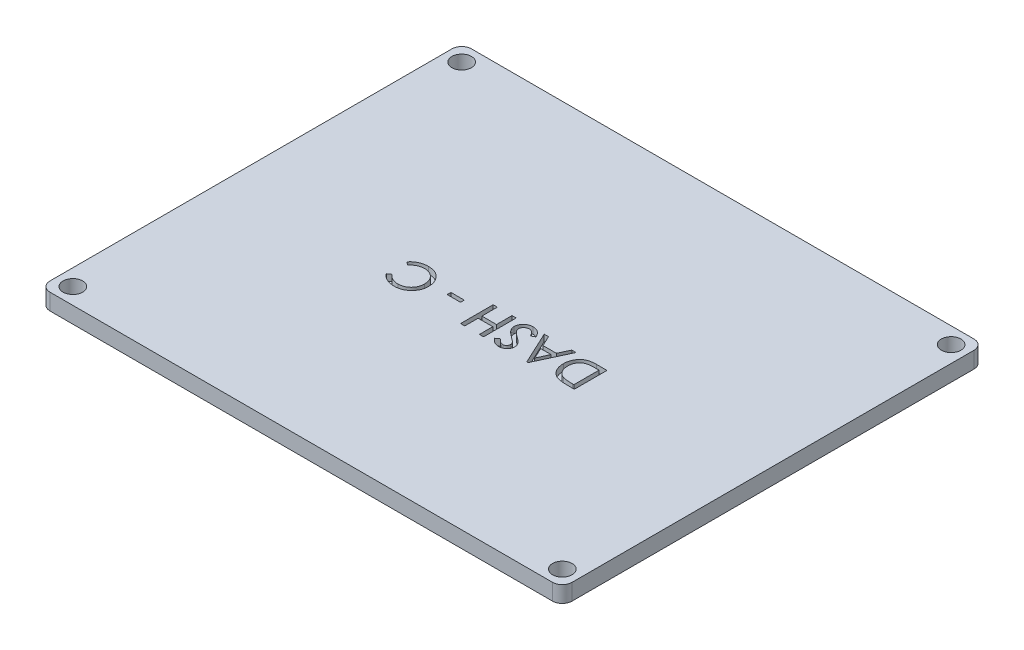
SolidWorks part; units mm, degrees
ref_plane "Front Plane" through (0, 0, 0) normal (0, 0, 1) x (1, 0, 0)
ref_plane "Top Plane" through (0, 0, 0) normal (0, 1, 0) x (1, 0, 0)
ref_plane "Right Plane" through (0, 0, 0) normal (1, 0, 0) x (0, 0, -1)
sketch "Sketch4" plane through (0, 0, 0) normal (0, 1, 0) x (1, 0, 0)
  line L0 (-3.7209, 2.8068) -> (2.7791, 2.8068)
  line L5 (5.2791, -38.8005) -> (5.2791, 22.7841) construction
  line L6 (3.7791, -40.3005) -> (-73.2209, -40.3005) construction
  line L7 (-74.7209, -38.8005) -> (-74.7209, 22.7841) construction
  line L8 (3.7791, 24.2841) -> (-73.2209, 24.2841) construction
  line L9 (5.2791, -38.8005) -> (5.2791, 22.7841)
  line L10 (3.7791, -40.3005) -> (-73.2209, -40.3005)
  line L11 (-74.7209, -38.8005) -> (-74.7209, 22.7841)
  line L12 (3.7791, 24.2841) -> (-73.2209, 24.2841)
  line L13 (-3.7209, 2.8068) -> (-3.7209, -18.8231)
  line L14 (-3.7209, -18.8231) -> (2.7791, -18.8231)
  line L21 (2.7791, -33.5578) -> (2.7791, 17.5415)
  line L22 (-67.9782, -37.8005) -> (-1.4635, -37.8005)
  line L23 (-72.2209, 17.5415) -> (-72.2209, -33.5578)
  line L24 (-1.4635, 21.7841) -> (-67.9782, 21.7841)
  line L25 (2.7791, -33.5578) -> (2.7791, 17.5415)
  line L26 (-67.9782, -37.8005) -> (-1.4635, -37.8005)
  line L27 (-72.2209, 17.5415) -> (-72.2209, -33.5578)
  line L28 (-1.4635, 21.7841) -> (-67.9782, 21.7841)
  circle A1 centre (2.7791, 21.7841) radius 1.5 construction
  circle A2 centre (-72.2209, 21.7841) radius 1.5
  circle A3 centre (-72.2209, 21.7841) radius 1.5
  arc A4 (5.2791, 22.7841) -> (3.7791, 24.2841) centre (3.7791, 22.7841) ccw construction
  circle A5 centre (2.7791, -37.8005) radius 1.5 construction
  arc A6 (3.7791, -40.3005) -> (5.2791, -38.8005) centre (3.7791, -38.8005) ccw construction
  arc A7 (-74.7209, -38.8005) -> (-73.2209, -40.3005) centre (-73.2209, -38.8005) ccw construction
  circle A8 centre (-72.2209, -37.8005) radius 1.5 construction
  arc A9 (-73.2209, 24.2841) -> (-74.7209, 22.7841) centre (-73.2209, 22.7841) ccw construction
  circle A10 centre (2.7791, 21.7841) radius 1.5
  arc A11 (5.2791, 22.7841) -> (3.7791, 24.2841) centre (3.7791, 22.7841) ccw
  circle A12 centre (2.7791, -37.8005) radius 1.5
  arc A13 (3.7791, -40.3005) -> (5.2791, -38.8005) centre (3.7791, -38.8005) ccw
  arc A14 (-74.7209, -38.8005) -> (-73.2209, -40.3005) centre (-73.2209, -38.8005) ccw
  circle A15 centre (-72.2209, -37.8005) radius 1.5
  arc A16 (-73.2209, 24.2841) -> (-74.7209, 22.7841) centre (-73.2209, 22.7841) ccw
  arc A41 (-0.0493, 20.7841) -> (-1.4635, 21.7841) centre (-1.4635, 20.2841) ccw
  arc A42 (-0.0493, 20.7841) -> (1.7791, 18.9557) centre (2.7791, 21.7841) ccw
  arc A43 (2.7791, 17.5415) -> (1.7791, 18.9557) centre (1.2791, 17.5415) ccw
  arc A44 (1.7791, -34.972) -> (2.7791, -33.5578) centre (1.2791, -33.5578) ccw
  arc A45 (1.7791, -34.972) -> (-0.0493, -36.8005) centre (2.7791, -37.8005) ccw
  arc A46 (-1.4635, -37.8005) -> (-0.0493, -36.8005) centre (-1.4635, -36.3005) ccw
  arc A47 (-69.3924, -36.8005) -> (-67.9782, -37.8005) centre (-67.9782, -36.3005) ccw
  arc A48 (-69.3924, -36.8005) -> (-71.2209, -34.972) centre (-72.2209, -37.8005) ccw
  arc A49 (-72.2209, -33.5578) -> (-71.2209, -34.972) centre (-70.7209, -33.5578) ccw
  arc A50 (-71.2209, 18.9557) -> (-72.2209, 17.5415) centre (-70.7209, 17.5415) ccw
  arc A51 (-71.2209, 18.9557) -> (-69.3924, 20.7841) centre (-72.2209, 21.7841) ccw
  arc A52 (-67.9782, 21.7841) -> (-69.3924, 20.7841) centre (-67.9782, 20.2841) ccw
  arc A53 (-0.0493, 20.7841) -> (-1.4635, 21.7841) centre (-1.4635, 20.2841) ccw
  arc A54 (-0.0493, 20.7841) -> (1.7791, 18.9557) centre (2.7791, 21.7841) ccw
  arc A55 (2.7791, 17.5415) -> (1.7791, 18.9557) centre (1.2791, 17.5415) ccw
  arc A56 (1.7791, -34.972) -> (2.7791, -33.5578) centre (1.2791, -33.5578) ccw
  arc A57 (1.7791, -34.972) -> (-0.0493, -36.8005) centre (2.7791, -37.8005) ccw
  arc A58 (-1.4635, -37.8005) -> (-0.0493, -36.8005) centre (-1.4635, -36.3005) ccw
  arc A59 (-69.3924, -36.8005) -> (-67.9782, -37.8005) centre (-67.9782, -36.3005) ccw
  arc A60 (-69.3924, -36.8005) -> (-71.2209, -34.972) centre (-72.2209, -37.8005) ccw
  arc A61 (-72.2209, -33.5578) -> (-71.2209, -34.972) centre (-70.7209, -33.5578) ccw
  arc A62 (-71.2209, 18.9557) -> (-72.2209, 17.5415) centre (-70.7209, 17.5415) ccw
  arc A63 (-71.2209, 18.9557) -> (-69.3924, 20.7841) centre (-72.2209, 21.7841) ccw
  arc A64 (-67.9782, 21.7841) -> (-69.3924, 20.7841) centre (-67.9782, 20.2841) ccw
  dimension "D1" = 0
  dimension "D2" = 0.5
extrude "BASE" add sketch "Sketch4" along normal blind 2.5 contours L28 A64 A63 A62 L27 A61 A60 A59 L26 A58 A57 A56 L25 A55 A54 A53 | L12 A16 L11 A14 L10 A13 L9 A11 A64 L28 A53 A54 A55 L25 A56 A57 A58 L26 A59 A60 A61 L27 A62 A63 A3 A10 A12 A15 | L28 | L14 L25 L0 L13 region at (-35.8413, 0, 8.0082) region at (-0.4709, 0, 8.0082) region at (4.1128, 0, 39.1341)
extrude "Boss-Extrude4" add sketch "Sketch4<3>" against normal blind 1 from surface contours L28 A64 A63 A62 L27 A61 A60 A59 L26 A58 A57 A56 L25 A55 A54 A53 region at (-35.8413, 0, 8.0082) starting at face at (-72.2209, 0, -20.2841)
sketch "Sketch4<3>" plane through (0, 0, 0) normal (0, 1, 0) x (1, 0, 0) same geometry as "Sketch4"
sketch "Sketch5" plane through (0, 2.5, 0) normal (0, 1, 0) x (1, 0, 0)
  line L0 (5.2791, -8.0082) -> (-74.7209, -8.0082) construction
  line L1 (5.2791, -38.8005) -> (5.2791, 22.7841) construction
  line L2 (-74.7209, -38.8005) -> (-74.7209, 22.7841) construction
  text T0 "<b>DASH - C</b>" font "Century Gothic" height 5
extrude "Cut-Extrude2" cut sketch "Sketch5" against normal blind 1
